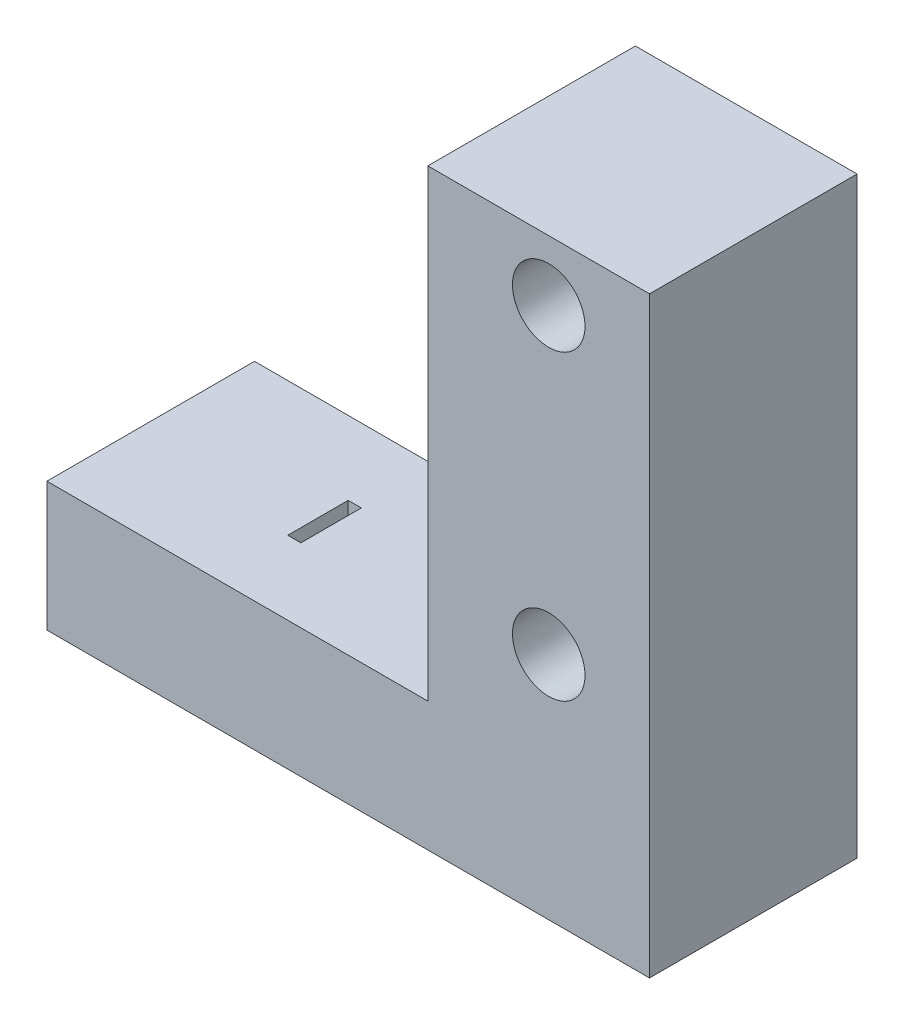
SolidWorks part; units mm, degrees
ref_plane "Front Plane" through (0, 0, 0) normal (0, 0, 1) x (1, 0, 0)
ref_plane "Top Plane" through (0, 0, 0) normal (0, 1, 0) x (1, 0, 0)
ref_plane "Right Plane" through (0, 0, 0) normal (1, 0, 0) x (0, 0, -1)
sketch "Sketch1" plane through (0, 0, 0) normal (0, 1, 0) x (1, 0, 0)
  line L0 (-14.25, 0) -> (0, 0) construction
  line L2 (-20.25, 5.15) -> (9.65, 5.15)
  line L3 (-20.25, 5.15) -> (-20.25, -5.15)
  line L4 (-20.25, -5.15) -> (9.65, -5.15)
  line L5 (9.65, 5.15) -> (9.65, -5.15)
  line L6 (-5.3, -5.15) -> (-5.3, 5.15) construction
  line L7 (-20.25, 0) -> (9.65, 0) construction
  circle A0 centre (0, 0) radius 2.4
  circle A1 centre (-14.25, 0) radius 2.4
  point P157 (-5.3, 0)
  dimension "D2" = 4.8
  dimension "D3" = 9.65
  dimension "D1" = 14.25
  dimension "D4" = 10.3
  dimension "D5" = 6
extrude "Boss-Extrude1" add sketch "Sketch1" along normal blind 30
sketch "Sketch4" plane through (0, 0, 0) normal (0, -1, 0) x (1, 0, 0)
  line L1 (-20.25, 5.15) -> (9.65, 5.15)
  line L2 (-20.25, 5.15) -> (-20.25, -5.15)
  line L3 (-20.25, -5.15) -> (9.65, -5.15)
  line L4 (9.65, 5.15) -> (9.65, -5.15)
  line L5 (-5.3, -5.15) -> (-5.3, 5.15) construction
  line L6 (-20.25, 0) -> (9.65, 0) construction
  point P268 (-5.3, 0)
extrude "Boss-Extrude3" add sketch "Sketch4" against normal up to surface (28 mm away) from offset 2 up to face at (0, 30, 2.4) offset against normal yes
sketch "Sketch2" plane through (0, 0, 5.15) normal (0, 0, 1) x (1, 0, 0)
  line L0 (9.65, 30) -> (9.65, 0) construction
  line L1 (-20.25, 30) -> (-1.35, 30)
  line L2 (-20.25, 30) -> (-20.25, 7)
  line L3 (-20.25, 7) -> (-1.35, 7)
  line L4 (-1.35, 30) -> (-1.35, 7)
  line L5 (-10.8, 7) -> (-10.8, 30) construction
  line L6 (-20.25, 18.5) -> (-1.35, 18.5) construction
  line L7 (-20.25, 0) -> (9.65, 0) construction
  point P320 (-10.8, 18.5)
  dimension "D1" = 11
  dimension "D2" = 7
extrude "Cut-Extrude1" cut sketch "Sketch2" against normal through all
sketch "Sketch3" plane through (0, 0, 0) normal (0, -1, 0) x (1, 0, 0)
  line L0 (-2.3, 0) -> (0, 0) construction
  line L1 (-11.95, 1.5) -> (-11.3, 1.5)
  line L2 (-11.95, 1.5) -> (-11.95, -1.5)
  line L3 (-11.95, -1.5) -> (-11.3, -1.5)
  line L4 (-11.3, 1.5) -> (-11.3, -1.5)
  line L5 (-11.625, -1.5) -> (-11.625, 1.5) construction
  line L6 (-11.95, 0) -> (-11.3, 0) construction
  line L7 (-2.95, 1.5) -> (-2.3, 1.5)
  line L8 (-2.95, 1.5) -> (-2.95, -1.5)
  line L9 (-2.95, -1.5) -> (-2.3, -1.5)
  line L10 (-2.3, 1.5) -> (-2.3, -1.5)
  line L11 (-2.625, -1.5) -> (-2.625, 1.5) construction
  line L12 (-2.95, 0) -> (-2.3, 0) construction
  circle A0 centre (0, 0) radius 2.4 construction
  circle A1 centre (-14.25, 0) radius 2.4 construction
  point P136 (-11.625, 0)
  point P157 (-2.625, 0)
  dimension "D1" = 0.65
  dimension "D2" = 3
  dimension "D3" = 0.1
  dimension "D4" = 0.1
extrude "Cut-Extrude2" cut sketch "Sketch3" against normal through all
hole_wizard "M3 Clearance Hole1" positions "Sketch5" profile "Sketch6" hole size "M3" standard "ANSI Metric" end condition through all
sketch "Sketch5" plane through (0, 0, 5.15) normal (0, 0, 1) x (1, 0, 0)
  line L0 (9.65, 30) -> (9.65, 0) construction
  line L1 (4.65, 27) -> (4.65, 12) construction
  point P0 (4.65, 12)
  point P2 (4.65, 27)
  dimension "D1" = 15
  dimension "D2" = 5
  dimension "D3" = 12
sketch "Sketch6" plane through (4.65, 12, 5.15) normal (1, 0, 0) x (0, -1, 0)
  line L0 (0, 0) -> (0, 10.3)
  line L1 (0, 10.3) -> (1.8, 10.3)
  line L2 (1.8, 10.3) -> (1.8, 0)
  line L5 (1.8, 0) -> (0, 0)
  line L11 (0, -6.35) -> (0, 107.95) construction
  dimension "Thru Hole Dia." = 3.6
  dimension "Thru Hole Depth" = 10.3
fillet "Fillet1" radius 1.5 4 edges at (-2.3, 1, 0.6856) (-2.3, 1, -0.6856) (-11.95, 1, -0.6856) (-11.95, 1, 0.6856)
chamfer "Chamfer1" distance 0.6 angle 45 16 edges at (-11.625, 0, -1.5) (-11.3, 0, 0) (-11.625, 0, 1.5) (-16.65, 0, 0) (-2.625, 0, -1.5) (2.4, 0, 0) (-2.625, 0, 1.5) (-2.95, 0, 0) (-5.3, 0, 5.15) (9.65, 0, 0) (-5.3, 0, -5.15) (-20.25, 0, 0) (-12.3515, 0, 1.6154) (-12.3515, 0, -1.6154) (-1.8985, 0, 1.6154) (-1.8985, 0, -1.6154)
